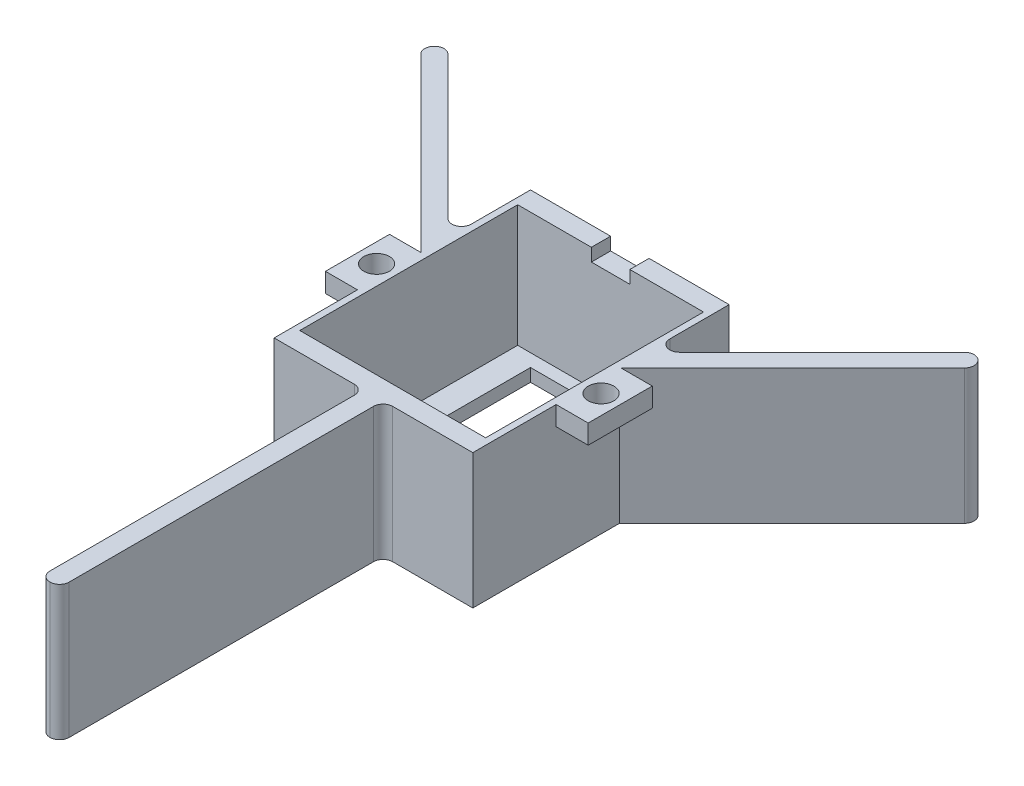
SolidWorks part; units mm, degrees
ref_plane "前视基准面" through (0, 0, 0) normal (0, 0, 1) x (1, 0, 0)
ref_plane "上视基准面" through (0, 0, 0) normal (0, 1, 0) x (1, 0, 0)
ref_plane "右视基准面" through (0, 0, 0) normal (1, 0, 0) x (0, 0, -1)
sketch "Sketch1" plane through (0, 0, 0) normal (0, 1, 0) x (1, 0, 0)
  line L0 (-10.5, -15) -> (10.5, -15)
  line L1 (-15.5, -20) -> (15.5, -20)
  line L2 (-15.5, -20) -> (-15.5, 20)
  line L3 (-15.5, 20) -> (15.5, 20)
  line L4 (15.5, -20) -> (15.5, 20)
  line L5 (-15.5, -20) -> (15.5, 20) construction
  line L6 (-15.5, 20) -> (15.5, -20) construction
  line L7 (10.5, -15) -> (10.5, 15)
  line L8 (-10.5, 15) -> (10.5, 15)
  line L9 (-10.5, -15) -> (-10.5, 15)
  dimension "D1" = 31
  dimension "D2" = 40
  dimension "D3" = 5
extrude "Boss-Extrude1" add sketch "Sketch1" along normal blind 2
sketch "Sketch2" plane through (0, 2, 0) normal (0, 1, 0) x (1, 0, 0)
  line L0 (-15.5, 20) -> (15.5, 20)
  line L1 (-15.5, -20) -> (15.5, -20)
  line L2 (-15.5, -20) -> (-15.5, 20)
  line L3 (14.5, 17) -> (-14.5, 17)
  line L4 (15.5, -20) -> (15.5, 20)
  line L5 (-15.5, -20) -> (15.5, 20) construction
  line L6 (-15.5, 20) -> (15.5, -20) construction
  line L7 (-14.5, -17) -> (14.5, -17)
  line L8 (-14.5, -17) -> (-14.5, 17)
  line L10 (14.5, -17) -> (14.5, 17)
  line L11 (-14.5, -17) -> (14.5, 17) construction
  line L12 (-14.5, 17) -> (14.5, -17) construction
  point P0 (0, 0)
  point P5 (0, 0)
  dimension "D1" = 1
  dimension "D2" = 3
extrude "Boss-Extrude2" add sketch "Sketch2" along normal blind 19
sketch "Sketch4" plane through (0, 21, 0) normal (0, 1, 0) x (1, 0, 0)
  line L1 (15.5, 3) -> (20.5, 3)
  line L2 (15.5, 3) -> (15.5, -7)
  line L3 (15.5, -7) -> (20.5, -7)
  line L4 (20.5, 3) -> (20.5, -7)
  line L5 (17.51, -2) -> (20.5, -2) construction
  line L6 (14.5, -17) -> (-14.5, -17) construction
  line L7 (14.5, 17) -> (14.5, -17) construction
  circle A0 centre (17.51, -2) radius 2
  dimension "D1" = 15
  dimension "D4" = 4
  dimension "D2" = 10
  dimension "D3" = 5
  dimension "D5" = 2.01
  dimension "D6" = 1
extrude "Boss-Extrude3" add sketch "Sketch4" against normal blind 3
mirror "Mirror1" about plane through (0, 0, 0) normal (1, 0, 0) of "Boss-Extrude3"
sketch "Sketch5" plane through (0, 0, 0) normal (0, -1, 0) x (1, 0, 0)
  line L1 (-1.5, 20) -> (1.5, 20)
  line L2 (-15.5, 20) -> (15.5, 20) construction
  line L3 (1.5, 20) -> (1.5, 70.4812)
  line L4 (-1.5, 20) -> (-1.5, 70.4812)
  line L5 (-1.5, 70.4812) -> (1.5, 70.4812)
  line L6 (0, 10.5) -> (0, 70.5) construction
  line L7 (-41.3525, -32.9738) -> (-43.4738, -30.8525)
  line L8 (0, 10.5) -> (42.4264, -31.9264) construction
  line L9 (15.5, -2.8787) -> (43.4738, -30.8525)
  line L10 (15.5, 20) -> (15.5, -20) construction
  line L11 (15.5, -7.1213) -> (41.3525, -32.9738)
  line L12 (41.3525, -32.9738) -> (43.4738, -30.8525)
  line L13 (15.5, -2.8787) -> (15.5, -7.1213)
  line L14 (-15.5, -7.1213) -> (-41.3525, -32.9738)
  line L15 (-15.5, -2.8787) -> (-15.5, -7.1213)
  line L16 (-15.5, -2.8787) -> (-43.4738, -30.8525)
  circle A0 centre (0, 10.5) radius 60 construction
  point P18 (15.5, -5)
  dimension "D1" = 135
  dimension "D4" = 120
  dimension "D2" = 3
  dimension "D3" = 9.5
extrude "Boss-Extrude4" add sketch "Sketch5" against normal up to surface (21 mm away) up to face at (0, 21, 1.3333)
fillet "Fillet2" radius 1.5 10 edges at (-41.3525, 10.5, -32.9738) (-43.4738, 10.5, -30.8525) (41.3525, 10.5, -32.9738) (43.4738, 10.5, -30.8525) (1.5, 10.5, 70.4812) (-1.5, 10.5, 70.4812) (-15.5, 10.5, -7.1213) (15.5, 10.5, -7.1213)
sketch "Sketch7" plane through (0, 21, 0) normal (0, 1, 0) x (1, 0, 0)
  line L0 (15.5, 20) -> (-15.5, 20) construction
  line L1 (-3, 20) -> (3, 20)
  line L2 (-3, 20) -> (-3, 17)
  line L3 (-3, 17) -> (3, 17)
  line L4 (3, 20) -> (3, 17)
  line L5 (14.5, 17) -> (-14.5, 17) construction
  point P8 (0, 20)
  dimension "D1" = 6
extrude "Cut-Extrude4" cut sketch "Sketch7" against normal blind 2
